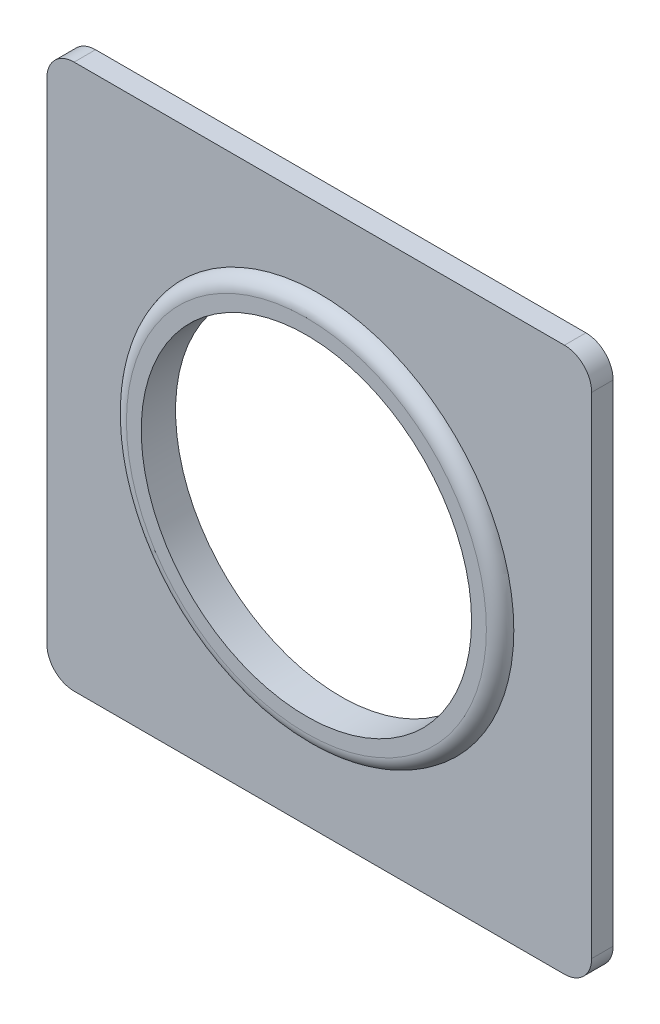
SolidWorks part; units mm, degrees
ref_plane "Front Plane" through (0, 0, 0) normal (0, 0, 1) x (1, 0, 0)
ref_plane "Top Plane" through (0, 0, 0) normal (0, 1, 0) x (1, 0, 0)
ref_plane "Right Plane" through (0, 0, 0) normal (1, 0, 0) x (0, 0, -1)
sketch "Sketch1" plane through (0, 0, 0) normal (0, 0, 1) x (1, 0, 0)
  line L1 (-63.5, -63.5) -> (-63.5, 63.5)
  line L2 (-60.5, -60.5) -> (60.5, -60.5)
  line L3 (-60.5, -60.5) -> (-60.5, 60.5)
  line L4 (-60.5, 60.5) -> (60.5, 60.5)
  line L5 (60.5, -60.5) -> (60.5, 60.5)
  line L6 (-60.5, -60.5) -> (60.5, 60.5) construction
  line L7 (-60.5, 60.5) -> (60.5, -60.5) construction
  line L8 (-63.5, 63.5) -> (63.5, 63.5)
  line L9 (63.5, -63.5) -> (63.5, 63.5)
  line L10 (-63.5, -63.5) -> (63.5, -63.5)
  circle A0 centre (0, 0) radius 44.45 construction
  circle A1 centre (0, 0) radius 38.5
  circle A2 centre (0, 0) radius 60.5 construction
  dimension "D1" = 88.9
  dimension "D2" = 77
  dimension "D3" = 121
  dimension "D4" = 3
sketch "Sketch2" plane through (0, 0, 0) normal (1, 0, 0) x (0, 0, -1)
  line L0 (0, 0) -> (22.225, 38.4948) construction
  line L1 (0, 0) -> (-17.0754, 0) construction
  line L2 (0, 0) -> (22.225, -38.4948) construction
  line L4 (22.225, 38.4948) -> (0, 38.4948) construction
  line L5 (0, 44.45) -> (0, -44.45) construction
  circle A0 centre (0, 0) radius 44.45 construction
  point P3 (0, 44.45)
  point P7 (0, 0)
  dimension "D1" = 88.9
  dimension "D2" = 120
extrude "Boss-Extrude1" add sketch "Sketch1" along normal blind 5 contours L1 L10 L9 L8 L5 L2 L3 L4 | L2 L5 L4 L3 A1 region at (-61.7039, 0, 0) region at (-58.7888, 0, 0)
sketch "Sketch3" plane through (0, 0, 5) normal (0, 0, 1) x (1, 0, 0)
  circle A0 centre (0, 0) radius 45.35
  circle A1 centre (0, 0) radius 38.5 construction
  circle A2 centre (0, 0) radius 38.5
  dimension "D1" = 6.85
  dimension "D2" = 6.85
extrude "Boss-Extrude2" add sketch "Sketch3" along normal blind 3
fillet "Fillet1" radius 6.35 4 edges at (63.5, 63.5, 2.5) (63.5, -63.5, 2.5) (-63.5, -63.5, 2.5) (-63.5, 63.5, 2.5)
fillet "Fillet2" radius 3.425 1 edges at (45.35, 0, 8)
